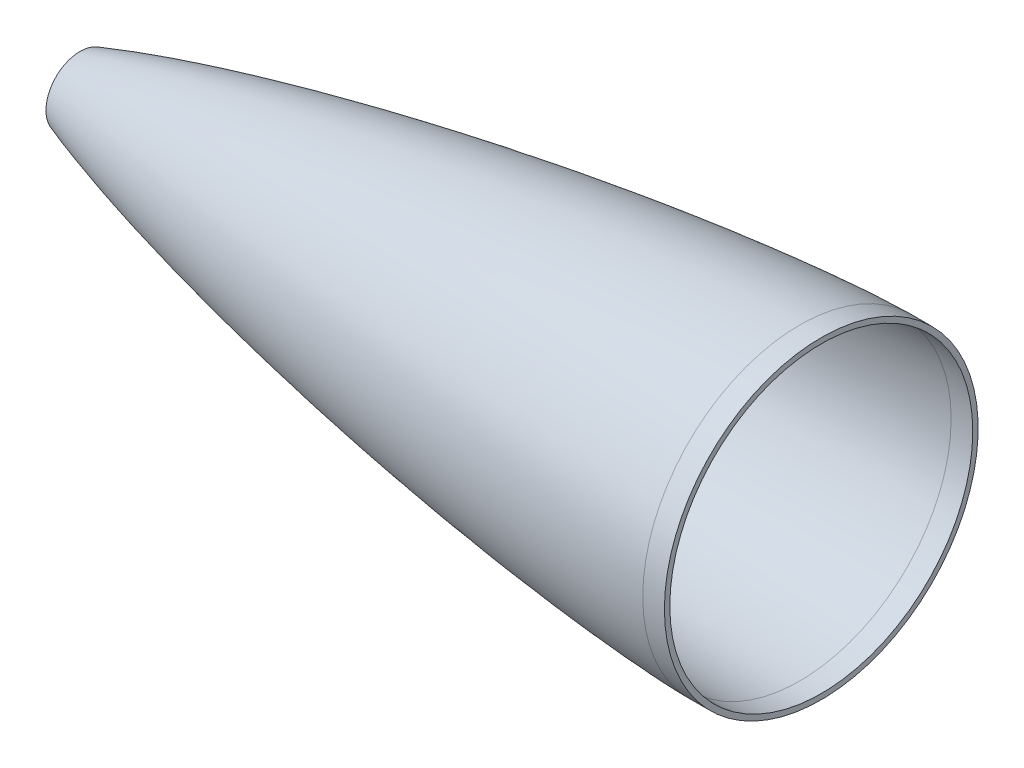
SolidWorks part; units mm, degrees
ref_plane "Front Plane" through (0, 0, 0) normal (0, 0, 1) x (1, 0, 0)
ref_plane "Top Plane" through (0, 0, 0) normal (0, 1, 0) x (1, 0, 0)
ref_plane "Right Plane" through (0, 0, 0) normal (1, 0, 0) x (0, 0, -1)
sketch "Sketch1" plane through (0, 0, 0) normal (0, 0, 1) x (1, 0, 0)
  line L0 (0, 0) -> (457.2, 0) construction
  line L2 (457.2, 88.9) -> (457.2, 0) construction
  line L5 (457.2, 0) -> (469.893, 0)
  line L7 (457.2, 88.9) -> (469.893, 88.9)
  line L8 (469.893, 0) -> (469.893, 88.9) construction
  line L12 (457.193, 92.075) -> (473.068, 92.075) construction
  line L13 (457.193, 92.075) -> (469.893, 92.075)
  line L14 (469.893, 92.075) -> (469.893, 88.9)
  line L15 (457.2, 0) -> (-3.2335, 0) construction
  line L16 (473.068, -3.175) -> (473.068, 92.075) construction
  line L17 (457.2, 0) -> (0, 0) construction
  line L18 (457.2, -3.175) -> (-3.846, -3.175) construction
  line L19 (457.2, -3.175) -> (473.068, -3.175) construction
  line L20 (-3.2335, 0) -> (0, 0)
  spline S0 degree 4 poles (0, 0) (0.0023, 0.0117) (0.0082, 0.0346) (0.0259, 0.0787) (0.0695, 0.163) (0.1339, 0.2631) (0.2191, 0.3779) (0.337, 0.5207) (0.5083, 0.7099) (0.7967, 0.9963) (1.2974, 1.437) (2.1714, 2.1155) (3.7007, 3.1561) (6.4159, 4.7683) (11.1362, 7.1982) (18.8825, 10.6592) (32.1618, 15.8286) (51.2292, 22.2419) (75.2304, 29.3379) (102.9883, 36.6578) (131.6198, 43.512) (160.3745, 49.8273) (189.2277, 55.6742) (218.164, 61.0945) (247.1725, 66.1133) (276.2458, 70.7417) (305.3786, 74.9797) (334.5673, 78.8147) (363.8094, 82.22) (389.4419, 84.7797) (411.4452, 86.618) (428.6335, 87.7745) (439.7385, 88.3707) (448.4263, 88.7187) (453.4393, 88.8519) (455.9463, 88.8945) (457.2, 88.9) knots 0 0 0 0 0 0.000101 0.000202 0.000405 0.000809 0.001116 0.001422 0.001985 0.002988 0.004584 0.007113 0.011426 0.01877 0.031526 0.052412 0.083828 0.140383 0.203215 0.266046 0.328877 0.391708 0.454539 0.51737 0.580202 0.643033 0.705864 0.768695 0.831526 0.894357 0.925773 0.957189 0.978594 0.989297 1 1 1 1 1 construction
  spline S1 degree 4 poles (0, 0) (0.0023, 0.0117) (0.0082, 0.0346) (0.0259, 0.0787) (0.0695, 0.163) (0.1339, 0.2631) (0.2191, 0.3779) (0.337, 0.5207) (0.5083, 0.7099) (0.7967, 0.9963) (1.2974, 1.437) (2.1714, 2.1155) (3.7007, 3.1561) (6.4159, 4.7683) (11.1362, 7.1982) (18.8825, 10.6592) (32.1618, 15.8286) (51.2292, 22.2419) (75.2304, 29.3379) (102.9883, 36.6578) (131.6198, 43.512) (160.3745, 49.8273) (189.2277, 55.6742) (218.164, 61.0945) (247.1725, 66.1133) (276.2458, 70.7417) (305.3786, 74.9797) (334.5673, 78.8147) (363.8094, 82.22) (389.4419, 84.7797) (411.4452, 86.618) (428.6335, 87.7745) (439.7385, 88.3707) (448.4263, 88.7187) (453.4393, 88.8519) (455.9463, 88.8945) (457.2, 88.9) knots 0 0 0 0 0 0.000101 0.000202 0.000405 0.000809 0.001116 0.001422 0.001985 0.002988 0.004584 0.007113 0.011426 0.01877 0.031526 0.052412 0.083828 0.140383 0.203215 0.266046 0.328877 0.391708 0.454539 0.51737 0.580202 0.643033 0.705864 0.768695 0.831526 0.894357 0.925773 0.957189 0.978594 0.989297 1 1 1 1 1
  spline S2 degree 1 poles (-3.846, -3.175) (457.193, 92.075) knots 0 0 1 1 construction
  spline S3 degree 3 poles (-3.846, -3.175) (-3.7875, -2.872) (-3.6999, -2.4175) (-3.583, -1.8115) (-3.4953, -1.357) (-3.4076, -0.9025) (-3.3346, -0.5238) (-3.2761, -0.2208) (-3.2396, -0.0314) (-3.2104, 0.1201) (-3.1885, 0.2337) (-3.1702, 0.3284) (-3.1556, 0.404) (-3.1445, 0.4613) (-3.1357, 0.5071) (-3.1278, 0.5481) (-3.1249, 0.5639) (-3.1177, 0.5989) (-3.1244, 0.5699) (-3.0927, 0.7218) (-3.063, 0.8419) (-3.0006, 1.0576) (-2.9108, 1.2891) (-2.84, 1.4442) (-2.7787, 1.5676) (-2.7032, 1.7081) (-2.6205, 1.8482) (-2.5281, 1.9921) (-2.3596, 2.2366) (-2.143, 2.509) (-1.8817, 2.8025) (-1.6375, 3.0537) (-1.3242, 3.3555) (-0.9484, 3.6886) (-0.5101, 4.0487) (0.0663, 4.4941) (0.7757, 5.0024) (1.6228, 5.5671) (2.4662, 6.0976) (3.3108, 6.6043) (4.4375, 7.2528) (5.8475, 8.0224) (7.5469, 8.8992) (9.2513, 9.7379) (11.53, 10.8156) (14.3926, 12.1) (17.8443, 13.5633) (22.465, 15.4324) (28.2731, 17.6418) (35.2787, 20.1426) (42.3159, 22.5242) (51.7325, 25.565) (63.5544, 29.1557) (77.8052, 33.2031) (92.1067, 37.0338) (106.4506, 40.6797) (120.8303, 44.1631) (140.0453, 48.6122) (164.1335, 53.8394) (193.1304, 59.6461) (222.2059, 65.0265) (251.351, 70.0043) (280.56, 74.5891) (309.8291, 78.7791) (339.1563, 82.5596) (368.5414, 85.8997) (393.0795, 88.2706) (412.7437, 89.865) (427.5134, 90.8847) (439.8371, 91.5549) (448.4929, 91.8903) (453.4377, 92.0259) (455.9439, 92.0695) (457.193, 92.075) knots -0.008181 -0.008181 -0.008181 -0.008181 -0.006212 -0.005227 -0.004243 -0.003258 -0.002273 -0.001781 -0.001289 -0.001043 -0.000797 -0.00055 -0.000427 -0.000304 -0.000181 -0.00012 -0.000058 -0.000027 0.000003 0.000019 0.000034 0.000065 0.000126 0.000188 0.00025 0.000311 0.000434 0.000557 0.00068 0.001173 0.001665 0.002157 0.002649 0.003634 0.004619 0.005603 0.007572 0.009541 0.011511 0.01348 0.015449 0.019387 0.023325 0.027264 0.031202 0.039078 0.046955 0.054831 0.070584 0.086338 0.102091 0.117844 0.14935 0.180856 0.212362 0.243868 0.275374 0.30688 0.369893 0.432905 0.495917 0.558929 0.621942 0.684954 0.747966 0.810978 0.87399 0.905497 0.937003 0.968509 0.984262 0.992138 1.000015 1.000015 1.000015 1.000015 only from (-3.2335, 0) to (457.193, 92.075)
  dimension "D1" = 457.2
  dimension "D3" = 12.7
  dimension "D4" = 3.175
revolve "Revolve3" add sketch "Sketch1" angle 360 about L0
ref_plane "Plane1" through (-3.2335, 0, 0) normal (1, 0, 0) x (0, 0, -1)
sketch "Sketch2" plane through (-3.2335, 0, 0) normal (1, 0, 0) x (0, 0, -1)
  circle A0 centre (0, 0) radius 92.075 construction
  circle A1 centre (0, 0) radius 92.075
extrude "Cut-Extrude1" cut sketch "Sketch2" along normal blind 38.1
